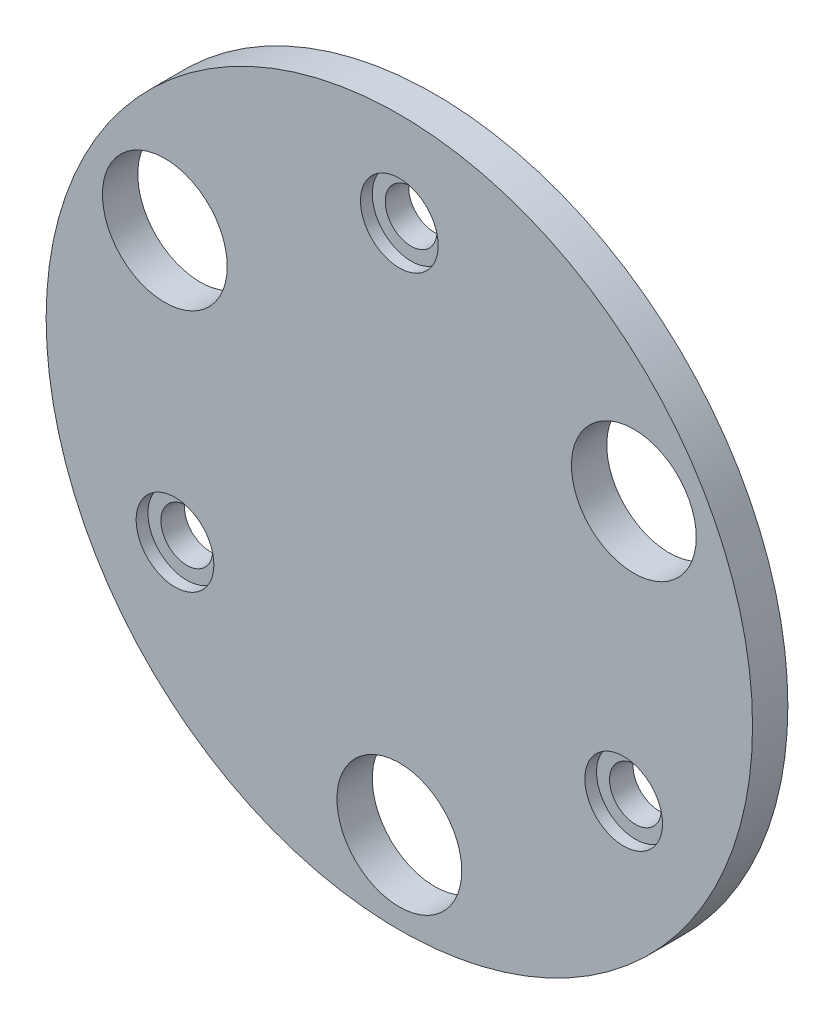
SolidWorks part; units mm, degrees
ref_plane "Front Plane" through (0, 0, 0) normal (0, 0, 1) x (1, 0, 0)
ref_plane "Top Plane" through (0, 0, 0) normal (0, 1, 0) x (1, 0, 0)
ref_plane "Right Plane" through (0, 0, 0) normal (1, 0, 0) x (0, 0, -1)
sketch "Sketch1" plane through (0, 0, 0) normal (0, 0, 1) x (1, 0, 0)
  line L0 (0, 0) -> (0, 15) construction
  line L1 (0, 0) -> (12.9904, 7.5) construction
  circle A0 centre (0, 0) radius 15
  circle A1 centre (9.9593, 5.75) radius 2.65
  circle A2 centre (0, -11.5) radius 2.65
  circle A3 centre (-9.9593, 5.75) radius 2.65
  circle A4 centre (0, 11) radius 1.1
  circle A5 centre (9.5263, -5.5) radius 1.1
  circle A6 centre (-9.5263, -5.5) radius 1.1
  circle A7 centre (0, 11) radius 1.65
  circle A8 centre (9.5263, -5.5) radius 1.65
  circle A9 centre (-9.5263, -5.5) radius 1.65
  point P8 (-9.5263, -5.5)
  point P14 (0, 0)
  point P20 (0, 0)
  point P26 (0, 0)
  dimension "D1" = 30
  dimension "D4" = 5.3
  dimension "D7" = 2.2
  dimension "D8" = 3
  dimension "D9" = 3.3
  dimension "D2" = 60
  dimension "D3" = 11.5
  dimension "D6" = 11
  dimension "D5" = 3
  dimension "D10" = 3
extrude "Boss-Extrude1" add sketch "Sketch1" along normal blind 1.5 contours A9 A6 | A7 A4 | A8 A5 | A0 A9 A8 A7 A3 A2 A1 region at (0, 0, 0) region at (-1.6033, 11, 0) region at (7.9229, -5.5, 0) region at (-11.1296, -5.5, 0)
extrude "Cut-Extrude1" cut sketch "Sketch1<5>" against normal blind 0.5 from surface contours A9 A6 | A7 A4 | A8 region at (-1.6033, 11, 0) region at (-11.1296, -5.5, 0) starting at face at (-8.4263, -5.5, 1.5)
sketch "Sketch1<5>" plane through (0, 0, 0) normal (0, 0, 1) x (1, 0, 0) same geometry as "Sketch1"
